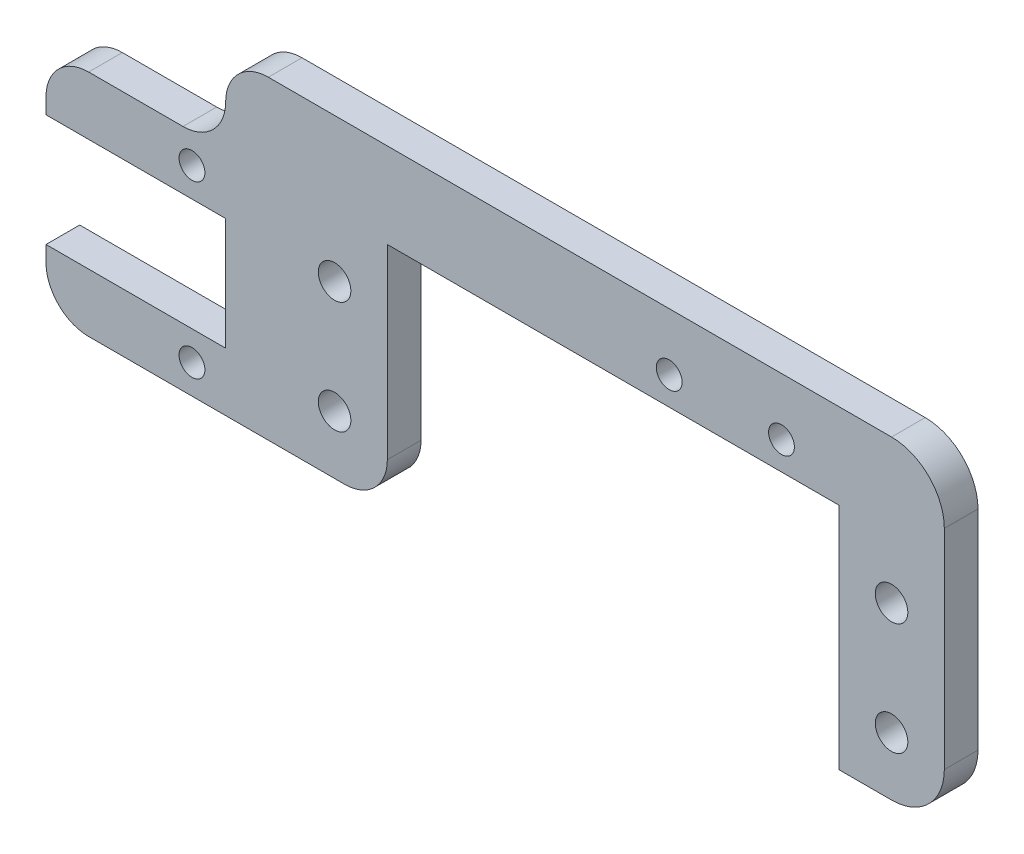
SolidWorks part; units mm, degrees
material "ABS"
ref_plane "Face" through (0, 0, 0) normal (0, 0, 1) x (1, 0, 0)
ref_plane "Dessus" through (0, 0, 0) normal (0, 1, 0) x (1, 0, 0)
ref_plane "Droite" through (0, 0, 0) normal (1, 0, 0) x (0, 0, -1)
sketch "Sketch10" plane through (0, 0, 0) normal (0, 0, 1) x (1, 0, 0)
  line L7 (22.4, 10.2) -> (62.6, 10.2)
  line L8 (62.6, 10.2) -> (62.6, -10.2)
  line L9 (62.6, -10.2) -> (72, -10.2)
  line L10 (8, 5) -> (-8, 5)
  line L11 (-8, 5) -> (-8, 10.2)
  line L15 (-8, -10.2) -> (-8, -5)
  line L16 (-8, -5) -> (8, -5)
  line L17 (8, -5) -> (8, 5)
  line L18 (-8, -10.2) -> (22.4, -10.2)
  line L19 (22.4, -10.2) -> (22.4, 10.2)
  line L20 (-8, 10.2) -> (8, 10.2)
  line L21 (8, 10.2) -> (8, 17.8)
  line L22 (8, 17.8) -> (72, 17.8)
  line L23 (72, -10.2) -> (72, 17.8)
  line L24 (-8, 5) -> (8, -5) construction
  line L25 (8, 5) -> (-8, -5) construction
  dimension "D1" = 5.2
  dimension "D3" = 10
  dimension "D4" = 40.2
  dimension "D5" = 9.4
  dimension "D6" = 12.8
  dimension "D7" = 20.4
  dimension "D8" = 16
  dimension "D9" = 64
extrude "Boss-Extrude7" add sketch "Sketch10" against normal blind 3
sketch "Sketch11" plane through (0, 0, 0) normal (0, 0, -1) x (-1, 0, 0)
  line L0 (-62.6, 0) -> (-22.4, 0) construction
  line L1 (-62.6, 10.2) -> (-62.6, -10.2) construction
  line L2 (-22.4, -10.2) -> (-22.4, 10.2) construction
  line L3 (-67.3, 5) -> (-67.3, -5) construction
  line L4 (-17.7, 5) -> (-17.7, -5) construction
  circle A0 centre (-67.3, -5) radius 1.45
  circle A4 centre (-17.7, -5) radius 1.45
  circle A5 centre (-17.7, 5) radius 1.45
  circle A6 centre (-67.3, 5) radius 1.45
  point P15 (-17.7, 0)
  dimension "D1" = 4.7
  dimension "D2" = 5.2
  dimension "D3" = 2.9
  dimension "D4" = 2
  dimension "D5" = 2
sketch "Sketch12" plane through (0, 0, 0) normal (0, 0, -1) x (-1, 0, 0)
  circle A0 centre (-57.5, 12.7) radius 1.15
  circle A2 centre (-47.5, 12.7) radius 1.15
  dimension "D3" = 2.3
  dimension "D1" = 5.1
  dimension "D2" = 2.5
  dimension "D4" = 2
extrude "Cut-Extrude3" cut sketch "Sketch12" along normal through all
extrude "Cut-Extrude4" cut sketch "Sketch11" along normal through all
sketch "Sketch13" plane through (0, 0, 0) normal (0, 0, 1) x (1, 0, 0)
  circle A0 centre (5, 7.6) radius 1.15
  circle A2 centre (5, -7.6) radius 1.15
  dimension "D2" = 2.6
  dimension "D3" = 2.3
  dimension "D1" = 3
  dimension "D4" = 2
extrude "Cut-Extrude5" cut sketch "Sketch13" against normal through all
fillet "Fillet1" radius 4.7 2 edges at (72, -10.2, -1.5) (72, 17.8, -1.5)
fillet "Fillet2" radius 3.8 5 edges at (22.4, -10.2, -1.5) (-8, -10.2, -1.5) (8, 17.8, -1.5) (8, 10.2, -1.5) (-8, 10.2, -1.5)
